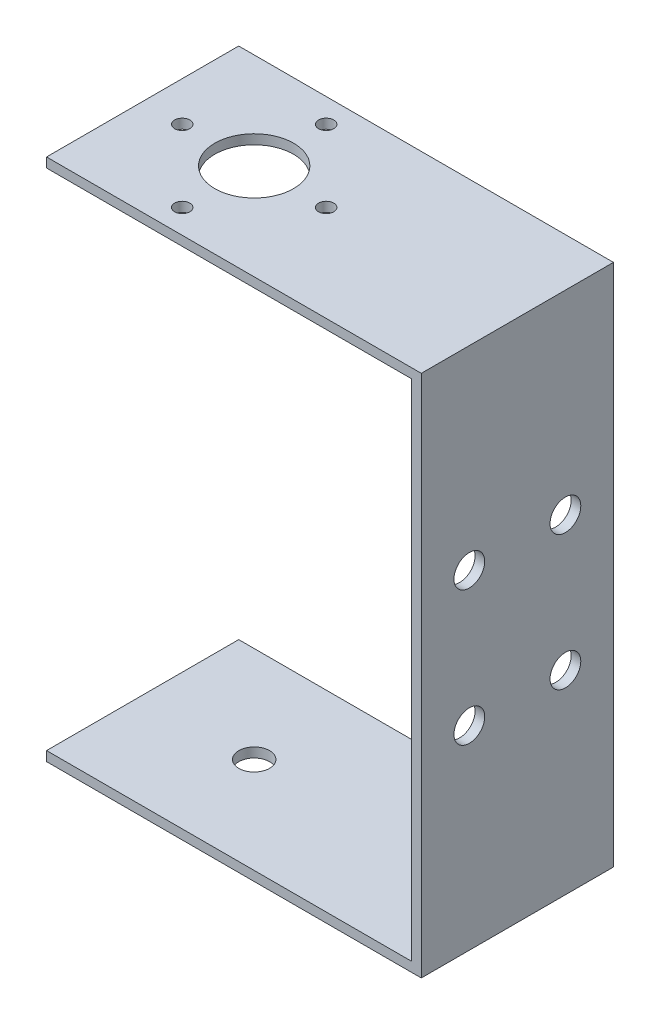
SolidWorks part; units mm, degrees
ref_plane "正面" through (0, 0, 0) normal (0, 0, 1) x (1, 0, 0)
ref_plane "平面" through (0, 0, 0) normal (0, 1, 0) x (1, 0, 0)
ref_plane "右側面" through (0, 0, 0) normal (1, 0, 0) x (0, 0, -1)
sketch "ｽｹｯﾁ1" plane through (0, 0, 0) normal (1, 0, 0) x (0, 0, -1)
  line L1 (0, 0) -> (20, 0)
  line L2 (0, 0) -> (0, 54.5)
  line L3 (0, 54.5) -> (20, 54.5)
  line L4 (20, 0) -> (20, 54.5)
extrude "ﾎﾞｽ - 押し出し1" add sketch "ｽｹｯﾁ1" along normal blind 1
sketch "ｽｹｯﾁ2" plane through (0, 0, 0) normal (-1, 0, 0) x (0, 0, 1)
  line L0 (0, 54.5) -> (0, 0) construction
  line L1 (-20, 54.5) -> (0, 54.5)
  line L2 (-20, 54.5) -> (-20, 53.5)
  line L3 (-20, 53.5) -> (0, 53.5)
  line L4 (0, 54.5) -> (0, 53.5)
extrude "ﾎﾞｽ - 押し出し2" add sketch "ｽｹｯﾁ2" along normal blind 38
sketch "ｽｹｯﾁ3" plane through (0, 0, 0) normal (-1, 0, 0) x (0, 0, 1)
  line L0 (-20, 0) -> (-20, 53.5) construction
  line L1 (0, 0) -> (-20, 0)
  line L2 (0, 0) -> (0, 1)
  line L3 (0, 1) -> (-20, 1)
  line L4 (-20, 0) -> (-20, 1)
extrude "ﾎﾞｽ - 押し出し3" add sketch "ｽｹｯﾁ3" along normal blind 38
sketch "ｽｹｯﾁ4" plane through (0, 54.5, 0) normal (0, 1, 0) x (1, 0, 0)
  circle A0 centre (-26.39, 10) radius 4.1
extrude "ｶｯﾄ - 押し出し1" cut sketch "ｽｹｯﾁ4" against normal blind 1
sketch "ｽｹｯﾁ5" plane through (0, 54.5, 0) normal (0, 1, 0) x (1, 0, 0)
  circle A0 centre (-33.88, 10) radius 0.79
extrude "ｶｯﾄ - 押し出し2" cut sketch "ｽｹｯﾁ5" against normal blind 1
sketch "ｽｹｯﾁ6" plane through (0, 54.5, 0) normal (0, 1, 0) x (1, 0, 0)
  circle A0 centre (-18.9, 10) radius 0.79
extrude "ｶｯﾄ - 押し出し3" cut sketch "ｽｹｯﾁ6" against normal blind 1
sketch "ｽｹｯﾁ7" plane through (0, 54.5, 0) normal (0, 1, 0) x (1, 0, 0)
  circle A0 centre (-26.39, 2.51) radius 0.79
extrude "ｶｯﾄ - 押し出し4" cut sketch "ｽｹｯﾁ7" against normal blind 1
sketch "ｽｹｯﾁ8" plane through (0, 54.5, 0) normal (0, 1, 0) x (1, 0, 0)
  circle A0 centre (-26.39, 17.49) radius 0.79
extrude "ｶｯﾄ - 押し出し5" cut sketch "ｽｹｯﾁ8" against normal blind 1
sketch "ｽｹｯﾁ9" plane through (0, 0, 0) normal (0, -1, 0) x (-1, 0, 0)
  circle A0 centre (26.39, 10) radius 1.6
extrude "ｶｯﾄ - 押し出し6" cut sketch "ｽｹｯﾁ9" against normal blind 1
sketch "ｽｹｯﾁ10" plane through (1, 0, 0) normal (1, 0, 0) x (0, 0, -1)
  circle A0 centre (5, 34.25) radius 1.6
extrude "ｶｯﾄ - 押し出し7" cut sketch "ｽｹｯﾁ10" against normal blind 1
sketch "ｽｹｯﾁ11" plane through (1, 0, 0) normal (1, 0, 0) x (0, 0, -1)
  circle A0 centre (15, 34.25) radius 1.6
extrude "ｶｯﾄ - 押し出し8" cut sketch "ｽｹｯﾁ11" against normal blind 1
sketch "ｽｹｯﾁ12" plane through (1, 0, 0) normal (1, 0, 0) x (0, 0, -1)
  circle A0 centre (5, 20.25) radius 1.6
extrude "ｶｯﾄ - 押し出し9" cut sketch "ｽｹｯﾁ12" against normal blind 1
sketch "ｽｹｯﾁ13" plane through (1, 0, 0) normal (1, 0, 0) x (0, 0, -1)
  circle A0 centre (15, 20.25) radius 1.6
extrude "ｶｯﾄ - 押し出し10" cut sketch "ｽｹｯﾁ13" against normal blind 1
